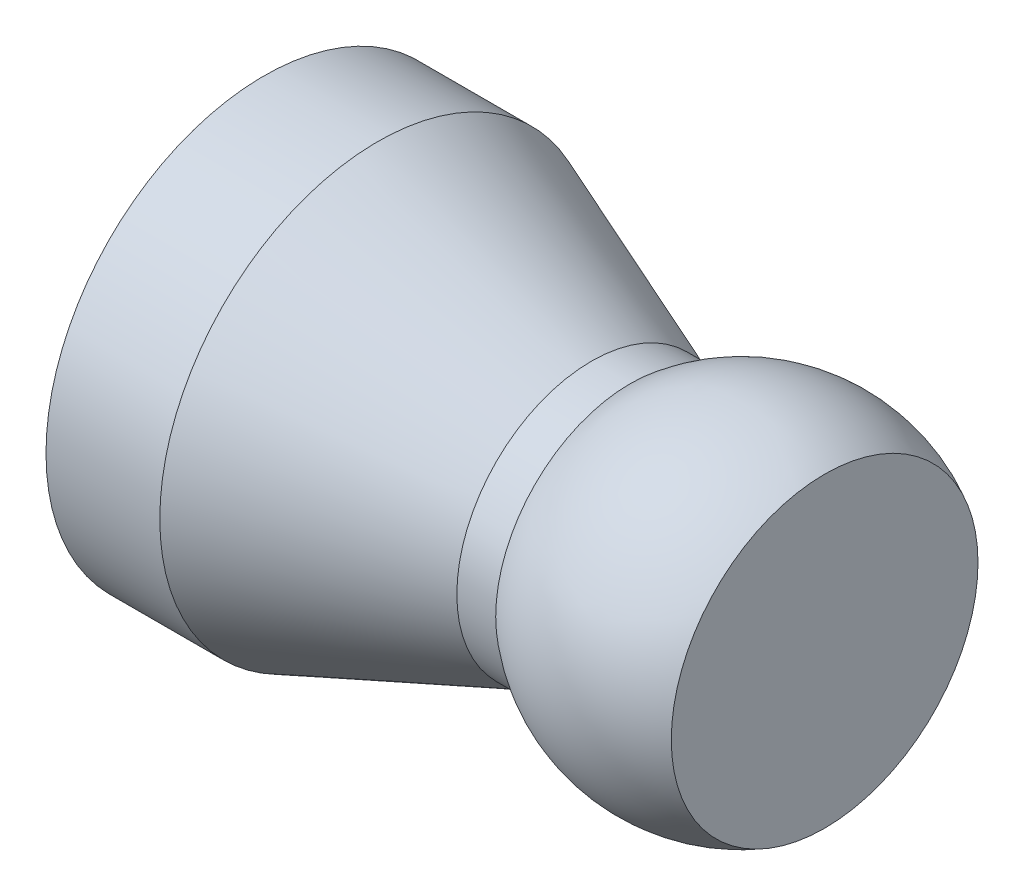
SolidWorks part; units mm, degrees
ref_plane "前视" through (0, 0, 0) normal (0, 0, 1) x (1, 0, 0)
ref_plane "上视" through (0, 0, 0) normal (0, 1, 0) x (1, 0, 0)
ref_plane "右视" through (0, 0, 0) normal (1, 0, 0) x (0, 0, -1)
sketch "草图1" plane through (0, 0, 0) normal (0, 0, 1) x (1, 0, 0)
  line L0 (0, 0) -> (0, 7.85)
  line L1 (0, 7.85) -> (4.1, 7.85)
  line L2 (4.1, 7.85) -> (11.8, 4.85)
  line L3 (11.8, 4.85) -> (13.2003, 4.85)
  line L4 (20.2, 5.5245) -> (20.2, 0)
  line L5 (20.2, 0) -> (0, 0)
  line L6 (20.2, 0) -> (0, 0) construction
  arc A0 (13.2003, 4.85) -> (20.2, 5.5245) centre (17.2, 0) cw
revolve "旋转1" add sketch "草图1" angle 360 about L6 reverse direction yes
sketch "草图2" plane through (0, 0, 0) normal (0, 0, 1) x (1, 0, 0)
  line L0 (8.9865, 0) -> (-3.5865, 0)
  line L1 (50, 0) -> (-50, 0) construction
  arc A0 (-3.5865, 0) -> (8.9865, 0) centre (2.7, 0) cw
revolve "切除-旋转1" cut sketch "草图2" angle 360 about L1 reverse direction yes
ref_plane "基准面1" through (0, 0, 0) normal (0, 0, 1) x (1, 0, 0)
ref_plane "body_to_con XY" through (0, 0, 0) normal (0, 0, 1) x (1, 0, 0)
ref_plane "body_to_con XZ" through (0, 0, 0) normal (0, -1, 0) x (-1, 0, 0)
ref_plane "body_to_con YZ" through (2.7, 0, 0) normal (1, 0, 0) x (0, 0, -1)
ref_axis "body_to_con X" through (-80.9, 0, 0) along (1, 0, 0)
ref_axis "body_to_con Y" through (2.7, -50, 0) along (0, 1, 0)
ref_axis "body_to_con Z" through (2.7, 0, 80.9) along (0, 0, -1)
sketch3d "body_to_con"
  point P0 (2.7, 0, 0)
